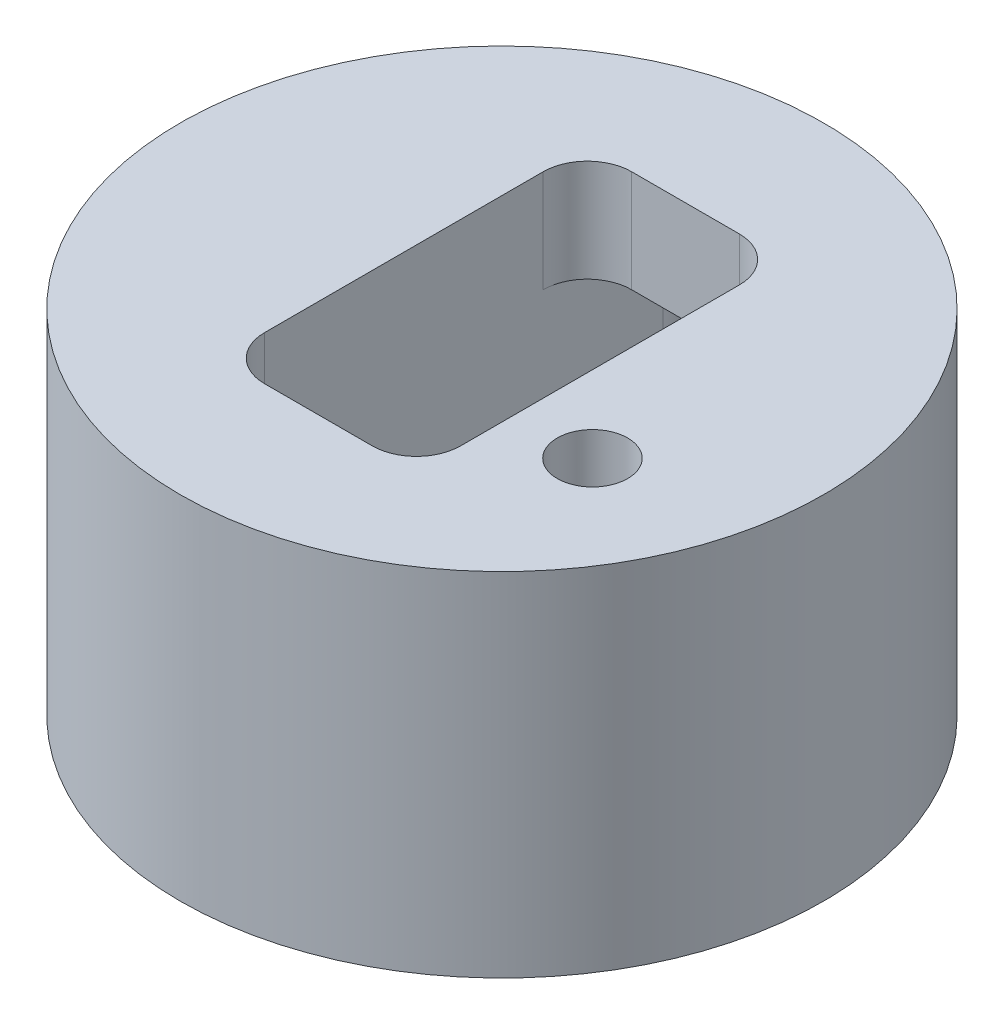
SolidWorks part; units mm, degrees
material "6061 Alloy"
ref_plane "Front Plane" through (0, 0, 0) normal (0, 0, 1) x (1, 0, 0)
ref_plane "Top Plane" through (0, 0, 0) normal (0, 1, 0) x (1, 0, 0)
ref_plane "Right Plane" through (0, 0, 0) normal (1, 0, 0) x (0, 0, -1)
sketch "main_features" plane through (0, 0, 0) normal (0, 1, 0) x (1, 0, 0)
  line L0 (0, 32) -> (0, -32) construction
  line L1 (5.35, 18.25) -> (-5.35, 18.25)
  line L2 (9.75, 13.85) -> (9.75, -13.85)
  line L3 (5.35, -18.25) -> (-5.35, -18.25)
  line L4 (-9.75, 13.85) -> (-9.75, -13.85)
  line L5 (9.75, 18.25) -> (-9.75, -18.25) construction
  line L6 (9.75, -18.25) -> (-9.75, 18.25) construction
  line L7 (-32, 0) -> (32, 0) construction
  line L9 (-7.25, 28.25) -> (7.25, 28.25)
  line L10 (-9.75, 25.75) -> (-9.75, -25.75)
  line L11 (-7.25, -28.25) -> (7.25, -28.25)
  line L12 (9.75, 25.75) -> (9.75, -25.75)
  line L13 (-9.75, 28.25) -> (9.75, -28.25) construction
  line L14 (-9.75, -28.25) -> (9.75, 28.25) construction
  circle A0 centre (0, 0) radius 32
  circle A1 centre (0, -23.5) radius 2 construction
  circle A2 centre (0, 23.5) radius 2 construction
  circle A3 centre (17.3707, 5.6062) radius 6.325 construction
  circle A4 centre (17.3707, -8.3699) radius 6.325 construction
  circle A5 centre (-17.3159, -8.3699) radius 6.325 construction
  circle A6 centre (-17.3159, 10.8238) radius 6.325 construction
  circle A7 centre (-6.7, -21.8) radius 0.85 construction
  arc A8 (-5.35, -18.25) -> (-9.75, -13.85) centre (-5.35, -13.85) cw
  arc A9 (9.75, -13.85) -> (5.35, -18.25) centre (5.35, -13.85) cw
  arc A10 (5.35, 18.25) -> (9.75, 13.85) centre (5.35, 13.85) cw
  arc A11 (-5.35, 18.25) -> (-9.75, 13.85) centre (-5.35, 13.85) ccw
  arc A12 (-9.75, -25.75) -> (-7.25, -28.25) centre (-7.25, -25.75) ccw
  arc A13 (7.25, -28.25) -> (9.75, -25.75) centre (7.25, -25.75) ccw
  arc A14 (7.25, 28.25) -> (9.75, 25.75) centre (7.25, 25.75) cw
  arc A15 (-7.25, 28.25) -> (-9.75, 25.75) centre (-7.25, 25.75) ccw
  point P53 (-6.3284, -21.8)
  dimension "D3" = 47
  dimension "D4" = 12.65
  dimension "D7" = 4.4
  dimension "D8" = 64
  dimension "D10" = 2.5
  dimension "D11" = 4
  dimension "D12" = 1.7
  dimension "D1" = 19.5
  dimension "D2" = 36.5
  dimension "D5" = 6.7
  dimension "D6" = 1.7
  dimension "D9" = 56.5
extrude "body" add sketch "main_features" along normal blind 35 contours A0 A15 L9 A14 L12 L2 A13 L11 A12 L10 L4 | L9 A15 L10 A11 L1 A10 L12 A14 | L11 A13 L12 A9 L3 A8 L10 A12 region at (0, 0, -22.9428) region at (0, 0, 22.9428) region at (-31.0949, 0, 0)
extrude "electrical_cutout" cut sketch "Sketch1<3>" along normal offset from surface (24.84 mm away) 10.16 contours L9 A15 L10 A11 L1 A10 L12 A14 | L11 A13 L12 A9 L3 A8 L10 A12 region at (0, 0, -22.9428) region at (0, 0, 22.9428) up to face at (0, 35, 0)
sketch "Sketch1<3>" plane through (0, 0, 0) normal (0, 1, 0) x (1, 0, 0) same geometry as "main_features"
hole_wizard "alignment_hole" positions "Sketch6" profile "Sketch7" hole size "Ø1.7" standard "ANSI Metric"
sketch "Sketch6" plane through (0, 24.84, 0) normal (0, 1, 0) x (1, 0, 0)
  point P0 (-6.7, -21.8)
sketch "Sketch7" plane through (-6.7, 24.84, 21.8) normal (1, 0, 0) x (0, 0, -1)
  line L0 (0, 0) -> (0, 5.5107)
  line L1 (0, 5.5107) -> (0.85, 5)
  line L2 (0.85, 5) -> (0.85, 0.025)
  line L3 (0.85, 0.025) -> (0.875, 0)
  line L5 (0.875, 0) -> (0, 0)
  line L6 (-0.85, 0.025) -> (-0.875, 0) construction
  line L10 (0, 5.5107) -> (-0.85, 5) construction
  line L11 (0, -6.35) -> (0, 107.95) construction
  dimension "Hole Dia." = 1.7
  dimension "Hole Depth" = 5
  dimension "Near C'Sink Dia." = 1.75
  dimension "Near C'Sink Angle" = 90
  dimension "Drill Angle" = 118
hole_wizard "electrical_mounting_holes" positions "Sketch8" profile "Sketch9" tap size "M6x1.0" standard "ANSI Metric"
sketch "Sketch8" plane through (0, 24.84, 0) normal (0, 1, 0) x (1, 0, 0)
  point P0 (0, -23.5)
  point P3 (0, 23.5)
sketch "Sketch9" plane through (0, 24.84, 23.5) normal (1, 0, 0) x (0, 0, -1)
  line L0 (0, 0) -> (0, 9.5022)
  line L1 (0, 9.5022) -> (2.5, 8)
  line L2 (2.5, 8) -> (2.5, 0.525)
  line L3 (2.5, 0.525) -> (3.025, 0)
  line L5 (3.025, 0) -> (0, 0)
  line L6 (-2.5, 0.525) -> (-3.025, 0) construction
  line L10 (0, 9.5022) -> (-2.5, 8) construction
  line L11 (0, -6.35) -> (0, 107.95) construction
  dimension "Tap Drill Dia." = 5
  dimension "Tap Drill Depth" = 8
  dimension "Near C'Sink Dia." = 6.05
  dimension "Near C'Sink Angle" = 90
  dimension "Drill Angle" = 118
cosmetic thread "Hole Thread5" parameters "D1"=7, "D2"=6
cosmetic thread "Hole Thread6" parameters "D1"=7, "D2"=6
ref_plane "Plane1" through (0, 0, 8.3699) normal (0, 0, 1) x (1, 0, 0)
sketch "push_connector" plane through (0, 0, 8.3699) normal (0, 0, 1) x (1, 0, 0)
  line L0 (17.3707, 0) -> (17.3707, 35)
  line L1 (32, 35) -> (-32, 35) construction
  line L2 (23.6957, 0) -> (11.0457, 0) construction
  line L3 (12.0707, 8) -> (22.6707, 8)
  line L4 (12.0707, 8) -> (12.0707, 0)
  line L5 (12.0707, 0) -> (22.6707, 0)
  line L6 (22.6707, 8) -> (22.6707, 0)
  line L7 (12.0707, 8) -> (22.6707, 0) construction
  line L8 (12.0707, 0) -> (22.6707, 8) construction
  line L10 (14.1457, 12.5) -> (20.5957, 12.5)
  line L11 (14.1457, 12.5) -> (14.1457, 0)
  line L12 (14.1457, 0) -> (20.5957, 0)
  line L13 (20.5957, 12.5) -> (20.5957, 0)
  line L14 (14.1457, 12.5) -> (20.5957, 0) construction
  line L15 (14.1457, 0) -> (20.5957, 12.5) construction
  line L16 (12.6957, 10.15) -> (22.0457, 10.15)
  line L17 (12.6957, 10.15) -> (12.6957, 0)
  line L18 (12.6957, 0) -> (22.0457, 0)
  line L19 (22.0457, 10.15) -> (22.0457, 0)
  line L20 (12.6957, 10.15) -> (22.0457, 0) construction
  line L21 (12.6957, 0) -> (22.0457, 10.15) construction
  line L23 (20.8707, 18.23) -> (13.8707, 18.23)
  line L24 (20.8707, 18.23) -> (20.8707, 35)
  line L25 (20.8707, 35) -> (13.8707, 35)
  line L26 (13.8707, 18.23) -> (13.8707, 35)
  line L27 (20.8707, 18.23) -> (13.8707, 35) construction
  line L28 (20.8707, 35) -> (13.8707, 18.23) construction
  line L29 (19.9707, 12.7626) -> (14.7707, 12.7626)
  line L30 (19.9707, 12.7626) -> (19.9707, 18.23)
  line L31 (19.9707, 18.23) -> (14.7707, 18.23)
  line L32 (14.7707, 12.7626) -> (14.7707, 18.23)
  line L33 (19.9707, 12.7626) -> (14.7707, 18.23) construction
  line L34 (19.9707, 18.23) -> (14.7707, 12.7626) construction
  point P5 (17.3707, 4)
  point P12 (17.3707, 6.25)
  point P17 (17.3707, 5.075)
  point P22 (17.3707, 26.5364)
  point P23 (17.3707, 26.615)
  point P28 (17.3707, 15.4963)
  point P33 (0, 0)
  point P34 (17.3707, 33.645)
  point P35 (0, 0)
  point P36 (14.7707, 22.4623)
  dimension "D1" = 10.6
  dimension "D2" = 9.35
  dimension "D3" = 10.15
  dimension "D4" = 6.45
  dimension "D5" = 12.5
  dimension "D6" = 8
  dimension "D7" = 7
  dimension "D8" = 5.2
  dimension "D9" = 16.77
revolve "push_connector_cutout" cut sketch "push_connector" angle 360 about L0 region at (15.7582, 4, 8.3699) region at (16.0707, 15.4963, 8.3699) region at (15.7582, 9.075, 8.3699) region at (13.4207, 4, 8.3699) region at (15.7582, 11.325, 8.3699) region at (13.4207, 9.075, 8.3699) region at (12.3832, 4, 8.3699) region at (15.6207, 26.615, 8.3699)
equation "\"od2\" = 9.35mm"
equation "\"od1\" = 10.6mm"
equation "\"h1\" = 8mm"
equation "\"h2\" = 10.15mm"
equation "\"od3\" = 6.45mm"
equation "\"h\" = 12.5mm"
equation "\"D1@push_connector\" = \"od1\""
equation "\"D2@push_connector\" = \"od2\""
equation "\"D3@push_connector\" = \"h2\""
equation "\"D4@push_connector\" = \"od3\""
equation "\"D5@push_connector\" = \"h\""
equation "\"D6@push_connector\" = \"h1\""
equation "\"schrader_depth\" = 16.77mm"
equation "\"D9@push_connector\"=\"schrader_depth\""
